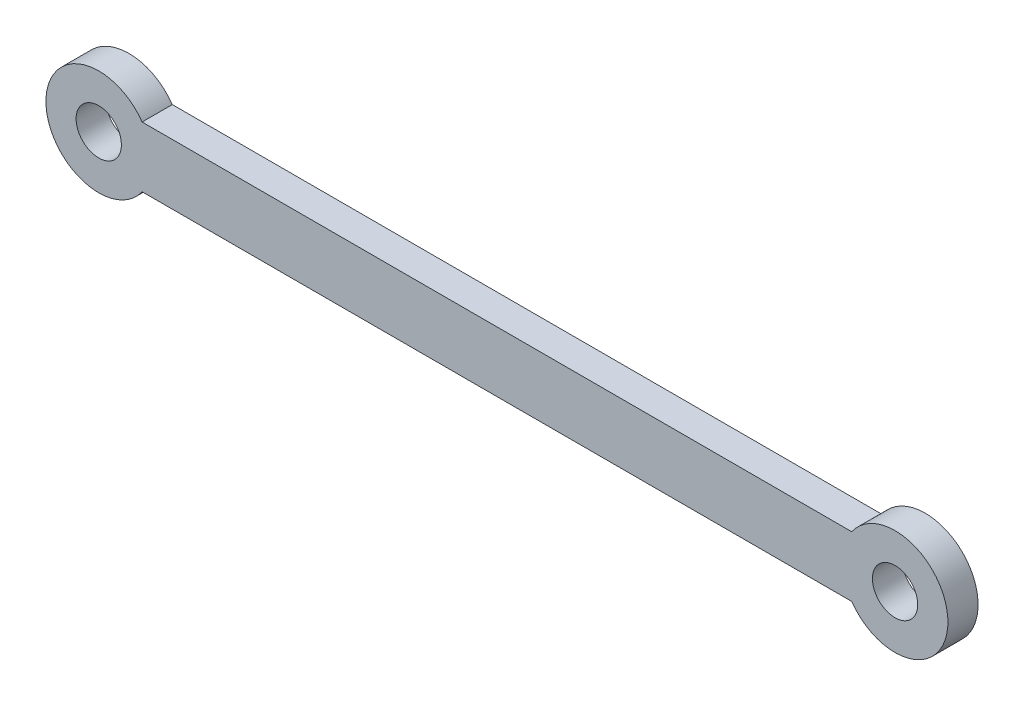
SolidWorks part; units mm, degrees
ref_plane "Alzado" through (0, 0, 0) normal (0, 0, 1) x (1, 0, 0)
ref_plane "Planta" through (0, 0, 0) normal (0, 1, 0) x (1, 0, 0)
ref_plane "Vista lateral" through (0, 0, 0) normal (1, 0, 0) x (0, 0, -1)
sketch "Croquis1" plane through (0, 0, 0) normal (0, 0, 1) x (1, 0, 0)
  line L0 (0, 0) -> (0, 50000) construction
  line L1 (0, 0) -> (50000, 0) construction
  line L2 (-23.5, -2) -> (23.5, -2)
  line L3 (-23.5, -2) -> (-23.5, 2)
  line L4 (-23.5, 2) -> (23.5, 2)
  line L5 (23.5, -2) -> (23.5, 2)
  line L6 (-23.5, -2) -> (23.5, 2) construction
  line L7 (-23.5, 2) -> (23.5, -2) construction
  circle A0 centre (-26.3723, 0) radius 3.5
  circle A1 centre (-26.3723, 0) radius 1.5
  circle A4 centre (26.3723, 0) radius 1.5
  circle A5 centre (26.3723, 0) radius 3.5
  point P5 (0, 0)
  dimension "D2" = 3
  dimension "D5" = 47
  dimension "D6" = 2
  dimension "D1" = 4
extrude "Saliente-Extruir1" add sketch "Croquis1" along normal blind 2 contours L2 A5 L4 A0 | L3 A0 A1 | A5 L5 A4 | L3 A0 | A5 L5 | A0 | A1 region at (0, 0, 0) region at (-29.7776, 0, 0) region at (-23.2469, 0, 0) region at (23.2469, 0, 0) region at (23.5947, 0, 0)
